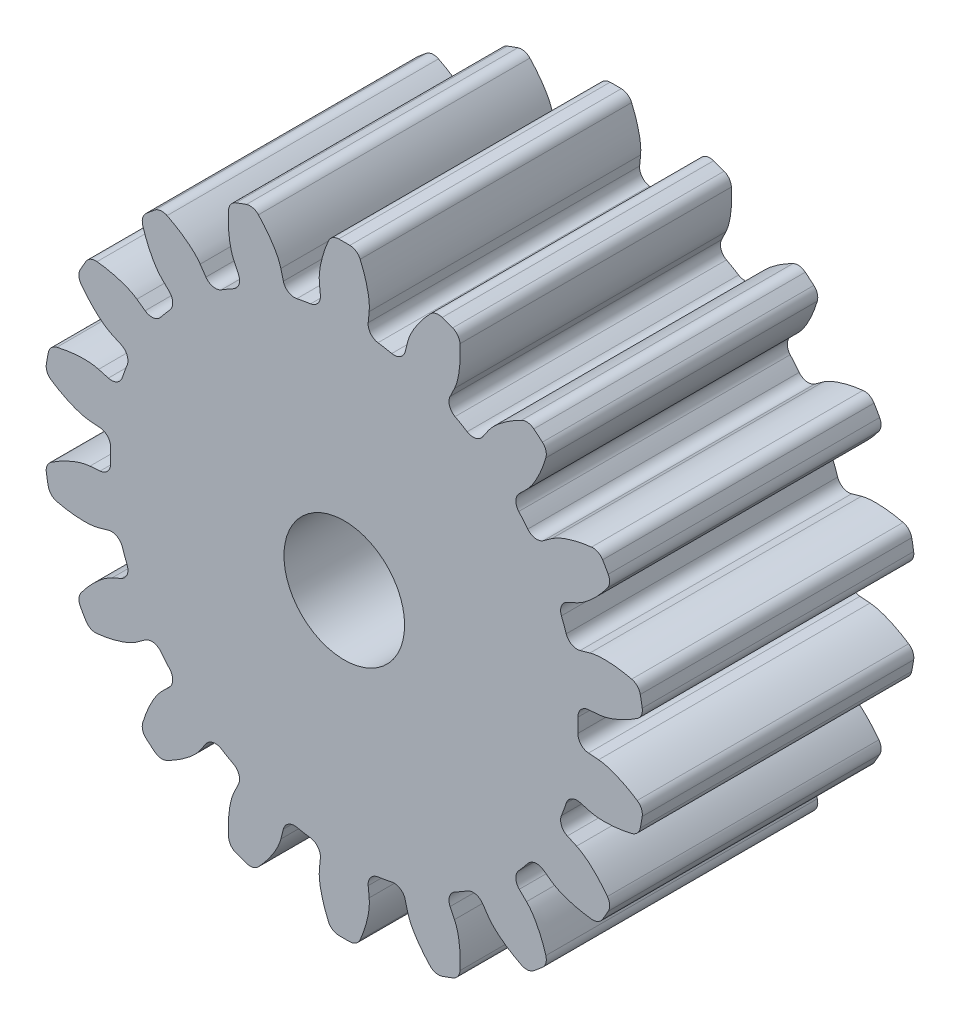
SolidWorks part; units mm, degrees
ref_plane "前视基准面" through (0, 0, 0) normal (0, 0, 1) x (1, 0, 0)
ref_plane "上视基准面" through (0, 0, 0) normal (0, 1, 0) x (1, 0, 0)
ref_plane "右视基准面" through (0, 0, 0) normal (1, 0, 0) x (0, 0, -1)
other "Configuration Table"
sketch "草图1" plane through (0, 0, 0) normal (0, 0, 1) x (1, 0, 0)
  line L0 (0, 0) -> (4.5, 0) construction
  line L1 (0, 0) -> (4.4829, 0.3922) construction
  line L2 (0, 0) -> (4.2162, 0.3242)
  line L3 (4.4829, 0.3922) -> (4.4829, -0.3922) construction
  line L4 (0, 0) -> (4.2162, -0.3242)
  circle A0 centre (0, 0) radius 5
  circle A1 centre (0, 0) radius 4.5 construction
  circle A2 centre (0, 0) radius 3.875
  circle A3 centre (0, 0) radius 4.2286 construction
  circle A4 centre (0, 0) radius 1
  spline S0 degree 4 poles (4.2162, 0.3242) (4.2483, 0.3267) (4.3375, 0.3403) (4.5024, 0.3926) (4.7554, 0.5133) (5.0556, 0.719) (5.3996, 1.035) (5.7429, 1.4621) (6.0488, 1.9801) (6.3604, 2.7282) (6.5454, 3.5193) (6.6174, 4.3594) (6.5658, 5.3616) (6.386, 6.3504) (6.0115, 7.457) (5.4105, 8.6071) (4.6509, 9.6584) (3.7565, 10.5972) (2.7501, 11.414) (1.6521, 12.1025) (0.4824, 12.659) (-0.5894, 13.0292) (-1.4522, 13.2437) (-2.0892, 13.3611) (-2.4865, 13.4209) (-2.8127, 13.4604) (-3.1237, 13.492) (-3.465, 13.5153) (-3.7294, 13.5295) (-4.0312, 13.5361) (-4.338, 13.5384) (-4.6432, 13.533) (-5.1827, 13.5111) (-5.559, 13.4725) (-5.9997, 13.426) (-6.2265, 13.3891) (-6.3687, 13.3688) (-6.431, 13.3583) knots 0 0 0 0 0 0.005604 0.015718 0.02996 0.048734 0.068727 0.096889 0.125051 0.153212 0.209535 0.237696 0.271429 0.327752 0.384075 0.440398 0.496721 0.553044 0.609367 0.66569 0.722013 0.778336 0.806497 0.820578 0.834659 0.84874 0.86282 0.876901 0.890982 0.900036 0.909091 0.931818 0.954545 0.977273 0.988636 1 1 1 1 1 construction
  spline S1 degree 4 poles (4.2162, 0.3242) (4.2483, 0.3267) (4.3375, 0.3403) (4.5024, 0.3926) (4.7554, 0.5133) (5.0556, 0.719) (5.3996, 1.035) (5.7429, 1.4621) (6.0488, 1.9801) (6.3604, 2.7282) (6.5454, 3.5193) (6.6174, 4.3594) (6.5658, 5.3616) (6.386, 6.3504) (6.0115, 7.457) (5.4105, 8.6071) (4.6509, 9.6584) (3.7565, 10.5972) (2.7501, 11.414) (1.6521, 12.1025) (0.4824, 12.659) (-0.5894, 13.0292) (-1.4522, 13.2437) (-2.0892, 13.3611) (-2.4865, 13.4209) (-2.8127, 13.4604) (-3.1237, 13.492) (-3.465, 13.5153) (-3.7294, 13.5295) (-4.0312, 13.5361) (-4.2111, 13.5375) (-4.3059, 13.5372) (-4.3531, 13.5368) knots 0 0 0 0 0 0.005604 0.015718 0.02996 0.048734 0.068727 0.096889 0.125051 0.153212 0.209535 0.237696 0.271429 0.327752 0.384075 0.440398 0.496721 0.553044 0.609367 0.66569 0.722013 0.778336 0.806497 0.820578 0.834659 0.84874 0.86282 0.876901 0.890982 0.900036 0.909091 0.909091 0.909091 0.909091 0.909091
  spline S2 degree 4 poles (4.2162, -0.3242) (4.2483, -0.3267) (4.3375, -0.3403) (4.5024, -0.3926) (4.7554, -0.5133) (5.0556, -0.719) (5.3996, -1.035) (5.7429, -1.4621) (6.0488, -1.9801) (6.3604, -2.7282) (6.5454, -3.5193) (6.6174, -4.3594) (6.5658, -5.3616) (6.386, -6.3504) (6.0115, -7.457) (5.4105, -8.6071) (4.6509, -9.6584) (3.7565, -10.5972) (2.7501, -11.414) (1.6521, -12.1025) (0.4824, -12.659) (-0.5894, -13.0292) (-1.4522, -13.2437) (-2.0892, -13.3611) (-2.4865, -13.4209) (-2.8127, -13.4604) (-3.1237, -13.492) (-3.465, -13.5153) (-3.7294, -13.5295) (-4.0312, -13.5361) (-4.338, -13.5384) (-4.6432, -13.533) (-5.1827, -13.5111) (-5.559, -13.4725) (-5.9997, -13.426) (-6.2265, -13.3891) (-6.3687, -13.3688) (-6.431, -13.3583) knots 0 0 0 0 0 0.005604 0.015718 0.02996 0.048734 0.068727 0.096889 0.125051 0.153212 0.209535 0.237696 0.271429 0.327752 0.384075 0.440398 0.496721 0.553044 0.609367 0.66569 0.722013 0.778336 0.806497 0.820578 0.834659 0.84874 0.86282 0.876901 0.890982 0.900036 0.909091 0.931818 0.954545 0.977273 0.988636 1 1 1 1 1 construction
  spline S3 degree 4 poles (4.2162, -0.3242) (4.2483, -0.3267) (4.3375, -0.3403) (4.5024, -0.3926) (4.7554, -0.5133) (5.0556, -0.719) (5.3996, -1.035) (5.7429, -1.4621) (6.0488, -1.9801) (6.3604, -2.7282) (6.5454, -3.5193) (6.6174, -4.3594) (6.5658, -5.3616) (6.386, -6.3504) (6.0115, -7.457) (5.4105, -8.6071) (4.6509, -9.6584) (3.7565, -10.5972) (2.7501, -11.414) (1.6521, -12.1025) (0.4824, -12.659) (-0.5894, -13.0292) (-1.4522, -13.2437) (-2.0892, -13.3611) (-2.4865, -13.4209) (-2.8127, -13.4604) (-3.1237, -13.492) (-3.465, -13.5153) (-3.7294, -13.5295) (-4.0312, -13.5361) (-4.2111, -13.5375) (-4.3059, -13.5372) (-4.3531, -13.5368) knots 0 0 0 0 0 0.005604 0.015718 0.02996 0.048734 0.068727 0.096889 0.125051 0.153212 0.209535 0.237696 0.271429 0.327752 0.384075 0.440398 0.496721 0.553044 0.609367 0.66569 0.722013 0.778336 0.806497 0.820578 0.834659 0.84874 0.86282 0.876901 0.890982 0.900036 0.909091 0.909091 0.909091 0.909091 0.909091
  point P15 (4.4829, 0)
  dimension "齿顶圆直径" = 10
  dimension "分度圆直径" = 9
  dimension "齿根圆直径" = 7.75
  dimension "基圆直径" = 8.4572
  dimension "内孔直径" = 2
  dimension "渐近线镜像线夹角" = 5
extrude "凸台-拉伸1" add sketch "草图1" along normal blind 4.5 contours A0 | A4
extrude "切除-拉伸1" cut sketch "草图1<3>" along normal through all contours A2 S3 A0 S1 region at (4.5106, 0, 0)
sketch "草图1<3>" plane through (0, 0, 0) normal (0, 0, 1) x (1, 0, 0) same geometry as "草图1"
fillet "圆角1" radius 0.19 4 edges at (4.9564, 0.6585, 2.25) (4.9564, -0.6585, 2.25) (3.8636, 0.2971, 2.25) (3.8636, -0.2971, 2.25)
pattern_circular "阵列(圆周)1" count 18 every 20 about axis through (0, 0, 4.5) along (0, 0, 1) of "切除-拉伸1", "圆角1"
equation "\"m\"= 0.5'模数"
equation "\"z\"= 18'齿数"
equation "\"a\"= 20度'压力角"
equation "\"d\"= \"m\" * \"z\"'分度圆直径"
equation "\"da\"= ( \"z\" + 2 ) * \"m\"'齿顶圆直径"
equation "\"df\"= ( \"z\" - 2.5 ) * \"m\"'齿根圆直径"
equation "\"s\"= 0.5 * PI * \"m\"'分度圆齿厚"
equation "\"r\"= 0.38 * \"m\"'齿根圆角"
equation "\"B\"= 0.3 * \"d\"'齿厚"
equation "\"db\"= \"m\" * \"z\" * cos ( \"a\" )'基圆直径"
equation "\"rb\"= \"db\" / 2'基圆半径"
equation "\"齿顶圆直径@草图1\"= \"da\""
equation "\"分度圆直径@草图1\"= \"d\""
equation "\"齿根圆直径@草图1\"= \"df\""
equation "\"基圆直径@草图1\"= \"db\""
equation "\"渐近线镜像线夹角@草图1\"= 360 / 4 / \"z\""
equation "\"h\"= 4.5'齿轮厚度"
equation "\"ir\"= 2'内孔直径"
equation "\"内孔直径@草图1\"= \"ir\""
equation "\"齿轮厚@凸台-拉伸1\"= \"h\""
equation "\"齿轮夹角@阵列(圆周)1\"= 360 / \"z\""
equation "\"齿数@阵列(圆周)1\"= \"z\""
equation "\"D1@圆角1\"=\"m\"*0.38"
